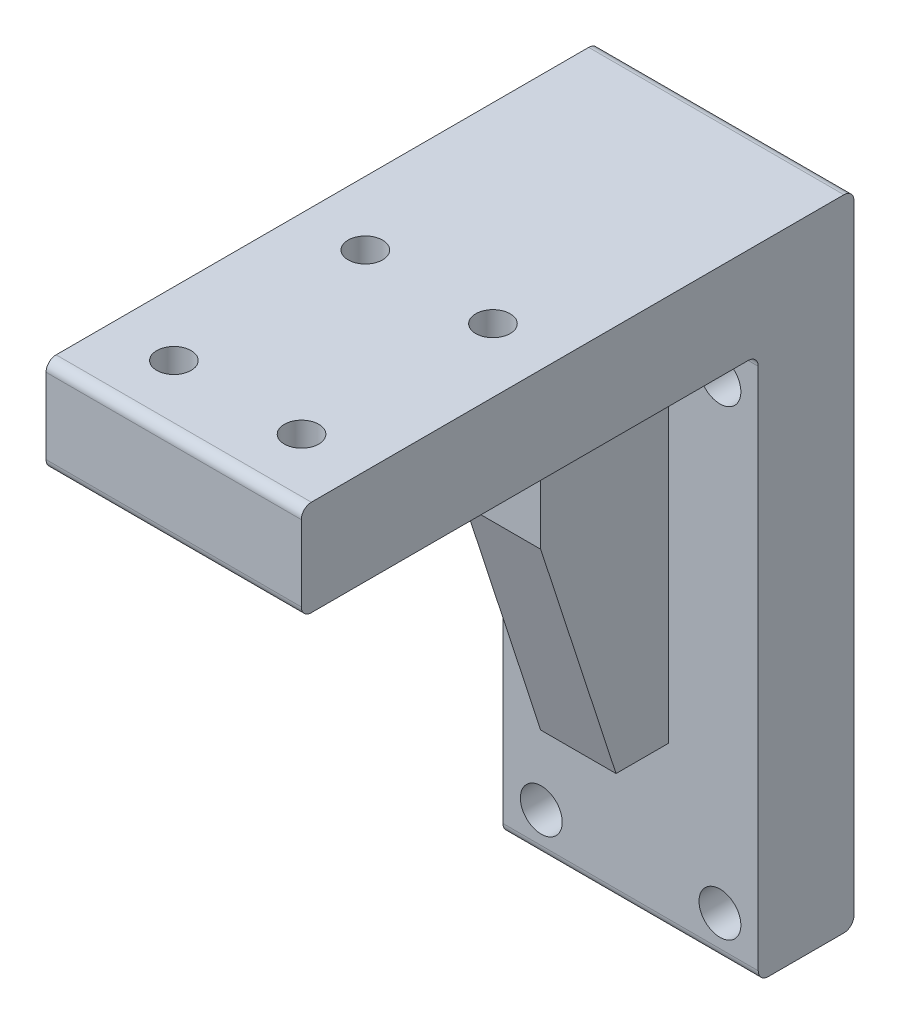
SolidWorks part; units mm, degrees
ref_plane "Front Plane" through (0, 0, 0) normal (0, 0, 1) x (1, 0, 0)
ref_plane "Top Plane" through (0, 0, 0) normal (0, 1, 0) x (1, 0, 0)
ref_plane "Right Plane" through (0, 0, 0) normal (1, 0, 0) x (0, 0, -1)
sketch "Sketch1" plane through (0, 0, 0) normal (0, 0, 1) x (1, 0, 0)
  line L0 (0, 0) -> (0, 19.05)
  line L1 (0, 0) -> (50.8, 0)
  line L2 (0, 0) -> (0, -108.204)
  line L3 (0, -108.204) -> (50.8, -108.204)
  line L4 (50.8, 0) -> (50.8, -108.204)
  line L5 (0, 19.05) -> (50.8, 19.05)
  line L6 (50.8, 19.05) -> (50.8, 0)
  circle A0 centre (7.62, -8.128) radius 4.1656
  circle A2 centre (43.18, -8.128) radius 4.1656
  circle A3 centre (7.62, -100.076) radius 4.1656
  circle A4 centre (43.18, -100.076) radius 4.1656
  dimension "D7" = 8.3312
  dimension "D1" = 35.56
  dimension "D2" = 91.948
  dimension "D3" = 108.204
  dimension "D4" = 50.8
  dimension "D5" = 7.62
  dimension "D6" = 8.128
  dimension "D8" = 19.05
extrude "Boss-Extrude1" add sketch "Sketch1" along normal blind 19.05 contours L4 L1 L2 L3 A4 A3 A2 A0 | L6 L5 L0 L1 region at (25.4, 9.525, 0) region at (25.4, -54.102, 0)
extrude "Boss-Extrude2" add sketch "Sketch1<3>" along normal blind 110 contours L6 L5 L0 L1 region at (25.4, 9.525, 0)
sketch "Sketch1<3>" plane through (0, 0, 0) normal (0, 0, 1) x (1, 0, 0) same geometry as "Sketch1"
ref_plane "Plane1" through (0, 19.05, 0) normal (0, 1, 0) x (1, 0, 0)
sketch "Sketch2" plane through (0, 19.05, 0) normal (0, 1, 0) x (1, 0, 0)
  line L0 (0, -110) -> (50.8, -110) construction
  line L1 (0, -110) -> (0, 0) construction
  line L2 (17.9, -19.05) -> (17.9, -44.45)
  line L3 (17.9, -44.45) -> (32.9, -44.45)
  line L4 (32.9, -44.45) -> (32.9, -19.05)
  line L5 (0, -19.05) -> (50.8, -19.05) construction
  line L6 (17.9, -19.05) -> (32.9, -19.05)
  circle A0 centre (12.7, -97.25) radius 3.425
  circle A1 centre (38.1, -97.25) radius 3.425
  circle A2 centre (12.7, -59.15) radius 3.425
  circle A3 centre (38.1, -59.15) radius 3.425
  dimension ".328" = 6.85
  dimension "1.5" = 25.4
  dimension "D1" = 38.1
  dimension ".75" = 12.75
  dimension "D2" = 12.7
  dimension "D3" = 15
  dimension "D4" = 25.4
  dimension "D5" = 25.4
  dimension "D6" = 5.2
extrude "Cut-Extrude1" cut sketch "Sketch2" against normal through all contours A2 | A0 | A1 | A3 region at (12.7, 19.05, 97.25) region at (38.1, 19.05, 97.25) region at (12.7, 19.05, 59.15) region at (38.1, 19.05, 59.15)
fillet "Fillet1" radius 2 6 edges at (25.4, 19.05, 0) (25.4, 0, 110) (25.4, 19.05, 110) (25.4, -108.204, 19.05) (25.4, -108.204, 0) (25.4, 0, 19.05)
extrude "Boss-Extrude3" add sketch "Sketch2<4>" against normal blind 95 contours L6 L2 L3 L4 region at (25.4, 19.05, 31.75)
sketch "Sketch2<4>" plane through (0, 19.05, 0) normal (0, 1, 0) x (1, 0, 0) same geometry as "Sketch2"
chamfer "Chamfer1" distance 15 angle 72 1 edges at (25.4, -75.95, 44.45) first distance on face at (25.4, -75.95, 31.75)
equation "\"D6@Sketch2\"=(\"D5@Sketch2\"-\"D3@Sketch2\")/2"
